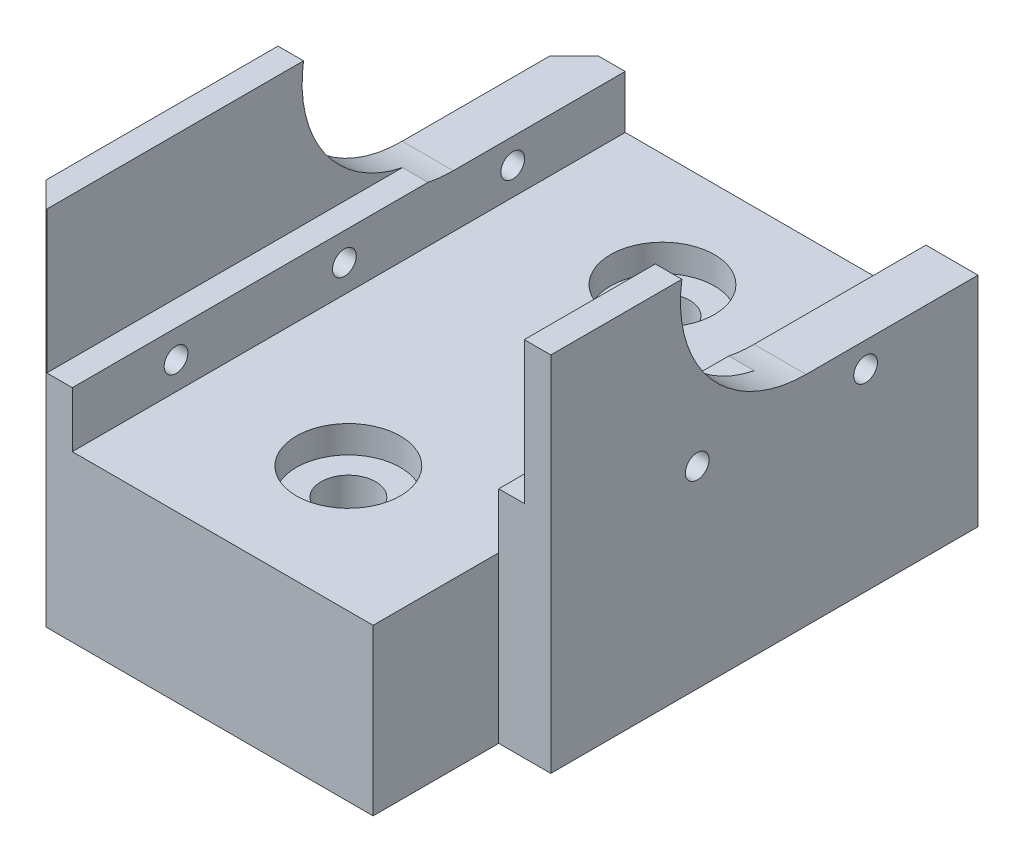
SolidWorks part; units mm, degrees
material "PLA"
ref_plane "Front Plane" through (0, 0, 0) normal (0, 0, 1) x (1, 0, 0)
ref_plane "Top Plane" through (0, 0, 0) normal (0, 1, 0) x (1, 0, 0)
ref_plane "Right Plane" through (0, 0, 0) normal (1, 0, 0) x (0, 0, -1)
sketch "Sketch1" plane through (0, 0, 0) normal (0, 1, 0) x (1, 0, 0)
  line L0 (-22.86, 30.48) -> (22.86, 30.48)
  line L6 (-22.86, 30.48) -> (-22.86, -30.48)
  line L8 (22.86, 30.48) -> (22.86, -30.48)
  line L9 (-22.86, -30.48) -> (22.86, -30.48)
  point P1 (-22.86, 0)
  point P7 (22.86, 0)
  dimension "D3" = 30.48
  dimension "D2" = 45.72
  dimension "D1" = 60.96
  dimension "D4" = 22.86
extrude "Boss-Extrude1" add sketch "Sketch1" along normal blind 6.35
sketch "Sketch2" plane through (0, 6.35, 0) normal (0, 1, 0) x (1, 0, 0)
  line L9 (-22.86, -30.48) -> (22.86, -30.48) construction
  line L10 (-22.86, 30.48) -> (-15.2, 30.48)
  line L11 (-22.86, 30.48) -> (-22.86, -30.48)
  line L12 (-22.86, -30.48) -> (-15.2, -30.48)
  line L13 (-15.2, 30.48) -> (-15.2, -30.48)
  line L14 (22.86, 30.48) -> (-22.86, 30.48) construction
  line L15 (15.2, 30.48) -> (22.86, 30.48)
  line L16 (15.2, 30.48) -> (15.2, -30.48)
  line L17 (15.2, -30.48) -> (22.86, -30.48)
  line L18 (22.86, 30.48) -> (22.86, -30.48)
  dimension "D1" = 7.66
  dimension "D2" = 7.66
extrude "Boss-Extrude2" add sketch "Sketch2" along normal blind 20.955
hole_wizard "M2 Clearance Hole2" positions "Sketch6" profile "Sketch7" hole size "M2" standard "ANSI Metric"
sketch "Sketch6" plane through (22.86, 0, 0) normal (1, 0, 0) x (0, 0, -1)
  line L0 (-30.48, 27.305) -> (-30.48, 0) construction
  line L1 (-30.48, 0) -> (30.48, 0) construction
  point P0 (-14.9172, 10.16)
  dimension "D1" = 15.5628
  dimension "D2" = 10.16
sketch "Sketch7" plane through (22.86, 10.16, 14.9172) normal (0, 1, 0) x (0, 0, -1)
  line L0 (0, 0) -> (0, 46.441)
  line L1 (0, 46.441) -> (1.2, 45.72)
  line L2 (1.2, 45.72) -> (1.2, 0)
  line L5 (1.2, 0) -> (0, 0)
  line L10 (0, 46.441) -> (-1.2, 45.72) construction
  line L11 (0, -6.35) -> (0, 107.95) construction
  dimension "Hole Dia." = 2.4
  dimension "Hole Depth" = 45.72
  dimension "Drill Angle" = 118
pattern_linear "LPattern1" count 3 spacing 17.018 along (0, 0, -1) of "M2 Clearance Hole2"
extrude "Boss-Extrude3" add sketch "Sketch1<3>" against normal blind 2.54
sketch "Sketch1<3>" plane through (0, 0, 0) normal (0, 1, 0) x (1, 0, 0) same geometry as "Sketch1"
sketch "Sketch8" plane through (-22.86, 0, 0) normal (-1, 0, 0) x (0, 0, 1)
  line L0 (-30.48, 27.305) -> (-30.48, -2.54) construction
  line L1 (-30.48, -2.54) -> (-14.605, -2.54)
  line L2 (-30.48, -2.54) -> (-30.48, 3.81)
  line L3 (-30.48, 3.81) -> (-14.605, 3.81)
  line L4 (-14.605, -2.54) -> (-14.605, 3.81)
  line L5 (-30.48, -2.54) -> (30.48, -2.54) construction
  dimension "D1" = 15.875
  dimension "D2" = 6.35
sketch "Sketch11" plane through (15.2, 0, 0) normal (-1, 0, 0) x (0, 0, 1)
  line L0 (30.48, 27.305) -> (30.48, 6.35) construction
  line L1 (-30.48, 27.305) -> (30.48, 27.305)
  line L2 (-30.48, 27.305) -> (-30.48, 12.96)
  line L3 (-30.48, 12.96) -> (30.48, 12.96)
  line L4 (30.48, 27.305) -> (30.48, 12.96)
  dimension "D1" = 14.345
extrude "Cut-Extrude1" cut sketch "Sketch11" against normal mid plane 35.56 from surface starting at plane "Right Plane"
sketch "Sketch12" plane through (22.86, 0, 0) normal (1, 0, 0) x (0, 0, -1)
  line L0 (30.48, 27.305) -> (30.48, -2.54) construction
  line L1 (13.105, 12.7) -> (30.48, 12.7)
  line L2 (30.48, 12.7) -> (30.48, 27.305)
  line L3 (30.48, 27.305) -> (25.6613, 27.305)
  line L5 (-30.48, 27.305) -> (30.48, 27.305) construction
  arc A0 (25.6613, 27.305) -> (13.105, 12.7) centre (13.105, 25.4) ccw
  dimension "D3" = 25.4
  dimension "D1" = 17.375
  dimension "D2" = 1.905
extrude "Cut-Extrude2" cut sketch "Sketch12" against normal through all
fillet "Fillet3" [suppressed] radius 0.762
sketch "Sketch17" plane through (0, -2.54, 0) normal (0, -1, 0) x (1, 0, 0)
  line L0 (-22.86, 30.48) -> (22.86, 30.48) construction
  line L1 (-22.86, 30.48) -> (22.86, 30.48)
  line L2 (-22.86, 30.48) -> (-22.86, -30.48)
  line L3 (-22.86, -30.48) -> (22.86, -30.48)
  line L4 (22.86, 30.48) -> (22.86, -30.48)
  line L5 (22.86, -30.48) -> (-22.86, -30.48) construction
  line L6 (22.86, 30.48) -> (22.86, -30.48) construction
  line L7 (-22.86, -30.48) -> (-22.86, 30.48) construction
extrude "Boss-Extrude4" add sketch "Sketch17" along normal blind 6.785
fillet "Fillet5" [suppressed] radius 0.762
sketch "Sketch19" plane through (0, 6.35, 0) normal (0, 1, 0) x (1, 0, 0)
  line L0 (15.2, 30.48) -> (15.2, -30.48) construction
  line L1 (-15.2, -30.48) -> (15.2, -30.48)
  line L2 (-15.2, -30.48) -> (-15.2, 30.48)
  line L3 (-15.2, 30.48) -> (15.2, 30.48)
  line L4 (15.2, -30.48) -> (15.2, 30.48)
  line L5 (15.2, 30.48) -> (-15.2, 30.48) construction
extrude "Boss-Extrude5" add sketch "Sketch19" along normal blind 1.01
hole_wizard "CBORE for M5 SBHCS2" positions "Sketch20" profile "Sketch21" counterbore size "M5" standard "ANSI Metric" end condition through all
sketch "Sketch20" plane through (0, 7.36, 0) normal (0, 1, 0) x (1, 0, 0)
  point P2 (0, -12.7)
  point P5 (0, 19.05)
  dimension "D1" = 31.75
  dimension "D2" = 12.7
sketch "Sketch21" plane through (0, 7.36, 12.7) normal (1, 0, 0) x (0, 0, 1)
  line L0 (0, 0) -> (0, 16.685)
  line L1 (0, 16.685) -> (2.75, 16.685)
  line L3 (2.75, 16.685) -> (2.75, 2.75)
  line L4 (2.75, 2.75) -> (5.25, 2.75)
  line L5 (5.25, 2.75) -> (5.25, 0)
  line L7 (5.25, 0) -> (0, 0)
  line L11 (0, -6.35) -> (0, 107.95) construction
  dimension "Thru Hole Dia." = 5.5
  dimension "Thru Hole Depth" = 16.685
  dimension "C'Bore Dia." = 10.5
  dimension "C'Bore Depth" = 2.75
fillet "Fillet6" [suppressed] radius 0.762
sketch "Sketch24" plane through (31.5712, -12.7, -14.6188) normal (0, 1, 0) x (0, 0, -1)
  line L0 (-45.0988, 8.7112) -> (-14.0701, 8.7112) construction
  line L1 (-45.0988, 54.4312) -> (-40.0188, 54.4312)
  line L2 (-45.0988, 54.4312) -> (-45.0988, 8.7112)
  line L3 (-45.0988, 8.7112) -> (-40.0188, 8.7112)
  line L4 (-40.0188, 54.4312) -> (-40.0188, 8.7112)
  dimension "D1" = 5.08
extrude "Cut-Extrude3" cut sketch "Sketch24" against normal through all both and the other way through all
sketch "Sketch25" plane through (0, 0, 25.4) normal (0, 0, 1) x (1, 0, 0)
  line L0 (15.2, -9.325) -> (15.2, 27.305)
  line L1 (22.86, -9.325) -> (-22.86, -9.325) construction
  line L3 (22.86, 27.305) -> (22.86, -9.325) construction
  line L4 (15.2, -9.325) -> (22.86, -9.325)
  line L5 (22.86, -9.325) -> (22.86, 27.305)
  line L6 (22.86, 27.305) -> (17.78, 27.305) construction
  line L7 (15.2, 27.305) -> (22.86, 27.305)
  line L8 (15.2, 12.96) -> (15.2, 7.36) construction
extrude "Cut-Extrude4" cut sketch "Sketch25" against normal blind 12.7
sketch "Sketch26" plane through (0, 0, 25.4) normal (0, 0, 1) x (1, 0, 0)
  line L0 (22.86, 27.305) -> (17.78, 27.305) construction
  line L1 (20.46, 27.305) -> (22.86, 27.305)
  line L2 (20.46, 27.305) -> (20.46, -9.325)
  line L3 (20.46, -9.325) -> (22.86, -9.325)
  line L4 (22.86, 27.305) -> (22.86, -9.325)
  line L5 (20.46, 27.305) -> (22.86, -9.325) construction
  line L6 (20.46, -9.325) -> (22.86, 27.305) construction
  line L8 (15.2, -9.325) -> (22.86, -9.325) construction
  line L9 (22.86, -9.325) -> (22.86, 27.305) construction
  point P0 (21.66, 8.99)
  point P5 (31.1556, 27.0821)
  dimension "D1" = 2.4
extrude "Cut-Extrude5" cut sketch "Sketch26" against normal through all
sketch "Sketch27" plane through (0, 0, 25.4) normal (0, 0, 1) x (1, 0, 0)
  line L0 (-17.78, 27.305) -> (-22.86, 27.305) construction
  line L1 (-22.86, 27.305) -> (-20.36, 27.305)
  line L2 (-22.86, 27.305) -> (-22.86, -9.325)
  line L3 (-22.86, -9.325) -> (-20.36, -9.325)
  line L4 (-20.36, 27.305) -> (-20.36, -9.325)
  line L5 (-22.86, 27.305) -> (-20.36, -9.325) construction
  line L6 (-22.86, -9.325) -> (-20.36, 27.305) construction
  line L7 (15.2, -9.325) -> (-22.86, -9.325) construction
  line L8 (-22.86, 27.305) -> (-22.86, -9.325) construction
  point P0 (-21.61, 8.99)
  dimension "D1" = 2.5
extrude "Cut-Extrude6" cut sketch "Sketch27" against normal through all
chamfer "Chamfer1" distance 2.5 angle 45 2 edges at (-20.36, 8.99, 25.4) (-20.36, 1.6875, -30.48)
